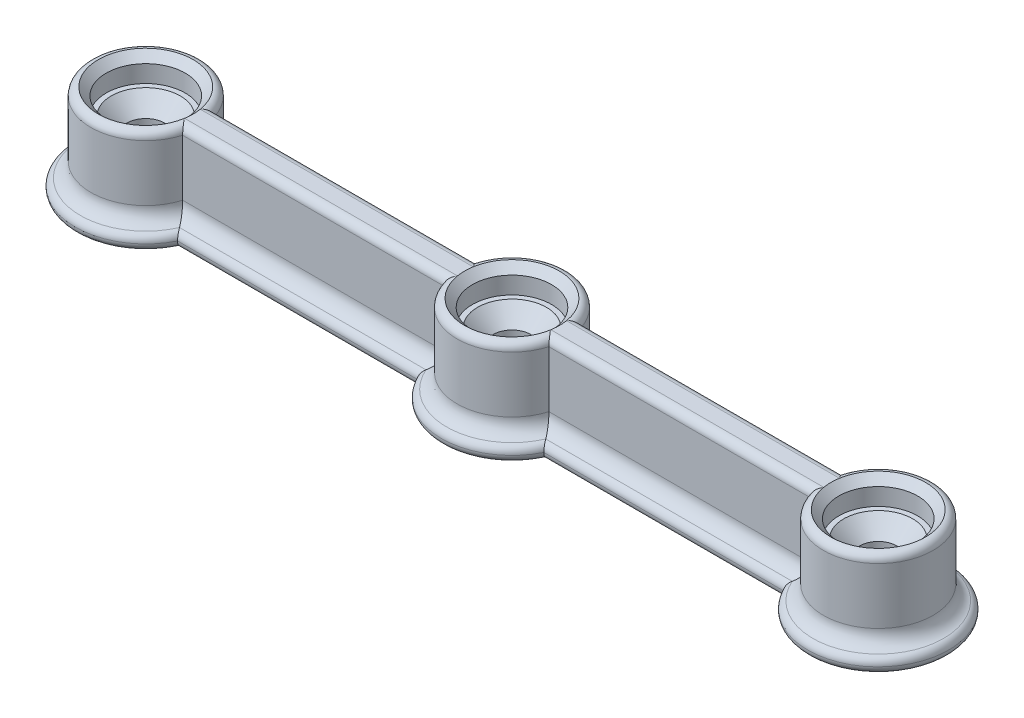
SolidWorks part; units mm, degrees
ref_plane "Front Plane" through (0, 0, 0) normal (0, 0, 1) x (1, 0, 0)
ref_plane "Top Plane" through (0, 0, 0) normal (0, 1, 0) x (1, 0, 0)
ref_plane "Right Plane" through (0, 0, 0) normal (1, 0, 0) x (0, 0, -1)
sketch "Sketch2" plane through (0, 0, 0) normal (0, 1, 0) x (1, 0, 0)
  line L0 (-31.7594, 1.5875) -> (-5.3246, 1.5875)
  line L3 (-31.7594, -1.5875) -> (-5.3246, -1.5875)
  line L4 (5.3246, 1.5875) -> (31.7594, 1.5875)
  line L5 (5.3246, -1.5875) -> (31.7594, -1.5875)
  arc A4 (-5.3246, -1.5875) -> (5.3246, -1.5875) centre (0, 0) ccw
  arc A5 (31.7594, -1.5875) -> (31.7594, 1.5875) centre (37.084, 0) ccw
  arc A6 (-31.7594, 1.5875) -> (-31.7594, -1.5875) centre (-37.084, 0) ccw
  arc A7 (5.3246, 1.5875) -> (-5.3246, 1.5875) centre (0, 0) ccw
  circle A8 centre (-37.084, 0) radius 1.905
  circle A9 centre (0, 0) radius 1.905
  circle A10 centre (37.084, 0) radius 1.905
  circle A11 centre (-37.084, 0) radius 7.366 construction
  circle A12 centre (37.084, 0) radius 7.366 construction
  dimension "D1" = 11.1125
  dimension "D5" = 3.81
  dimension "D4" = 3.175
extrude "Boss-Extrude1" add sketch "Sketch2" along normal blind 9.525
sketch "Sketch4" plane through (0, 0, 0) normal (0, -1, 0) x (1, 0, 0)
  line L9 (-6.3994, 3.175) -> (-30.6846, 3.175)
  line L10 (-30.6846, -3.175) -> (-6.3994, -3.175)
  line L11 (6.3994, -3.175) -> (30.6846, -3.175)
  line L12 (30.6846, 3.175) -> (6.3994, 3.175)
  line L13 (-6.3994, 3.175) -> (-30.6846, 3.175)
  line L14 (-30.6846, -3.175) -> (-6.3994, -3.175)
  line L15 (6.3994, -3.175) -> (30.6846, -3.175)
  line L16 (30.6846, 3.175) -> (6.3994, 3.175)
  line L18 (-5.3246, 1.5875) -> (-31.7594, 1.5875)
  line L19 (-31.7594, -1.5875) -> (-5.3246, -1.5875)
  line L20 (5.3246, -1.5875) -> (31.7594, -1.5875)
  line L21 (31.7594, 1.5875) -> (5.3246, 1.5875)
  line L22 (-5.3246, 1.5875) -> (-31.7594, 1.5875)
  line L23 (-31.7594, -1.5875) -> (-5.3246, -1.5875)
  line L24 (5.3246, -1.5875) -> (31.7594, -1.5875)
  line L25 (31.7594, 1.5875) -> (5.3246, 1.5875)
  arc A8 (6.3994, 3.175) -> (-6.3994, 3.175) centre (0, 0) ccw
  arc A9 (-30.6846, 3.175) -> (-30.6846, -3.175) centre (-37.084, 0) ccw
  arc A10 (-6.3994, -3.175) -> (6.3994, -3.175) centre (0, 0) ccw
  arc A11 (30.6846, -3.175) -> (30.6846, 3.175) centre (37.084, 0) ccw
  arc A12 (6.3994, 3.175) -> (-6.3994, 3.175) centre (0, 0) ccw
  arc A13 (-30.6846, 3.175) -> (-30.6846, -3.175) centre (-37.084, 0) ccw
  arc A14 (-6.3994, -3.175) -> (6.3994, -3.175) centre (0, 0) ccw
  arc A15 (30.6846, -3.175) -> (30.6846, 3.175) centre (37.084, 0) ccw
  arc A16 (5.3246, 1.5875) -> (-5.3246, 1.5875) centre (0, 0) ccw
  arc A17 (-31.7594, 1.5875) -> (-31.7594, -1.5875) centre (-37.084, 0) ccw
  arc A18 (-5.3246, -1.5875) -> (5.3246, -1.5875) centre (0, 0) ccw
  arc A19 (31.7594, -1.5875) -> (31.7594, 1.5875) centre (37.084, 0) ccw
  arc A20 (5.3246, 1.5875) -> (-5.3246, 1.5875) centre (0, 0) ccw
  arc A21 (-31.7594, 1.5875) -> (-31.7594, -1.5875) centre (-37.084, 0) ccw
  arc A22 (-5.3246, -1.5875) -> (5.3246, -1.5875) centre (0, 0) ccw
  arc A23 (31.7594, -1.5875) -> (31.7594, 1.5875) centre (37.084, 0) ccw
  dimension "D1" = 1.5875
  dimension "D2" = 0
extrude "Boss-Extrude2" add sketch "Sketch4" against normal blind 1.5875
sketch "Sketch3" plane through (0, 9.525, 0) normal (0, 1, 0) x (1, 0, 0)
  circle A0 centre (0, 0) radius 4.0005
  circle A1 centre (-37.084, 0) radius 4.0005
  circle A2 centre (37.084, 0) radius 4.0005
  dimension "D1" = 8.001
extrude "Cut-Extrude1" cut sketch "Sketch3" against normal blind 2.54
fillet "Fillet3" radius 0.7937 16 edges at (18.542, 0, 3.175) (44.2277, 0, 0) (18.542, 0, -3.175) (0, 0, -7.1438) (-18.542, 0, -3.175) (-44.2278, 0, 0) (-18.542, 0, 3.175) (0, 0, 7.1437) (-18.542, 1.5875, 3.175) (-44.2278, 1.5875, 0) (-18.542, 1.5875, -3.175) (0, 1.5875, -7.1438) (18.542, 1.5875, -3.175) (44.2277, 1.5875, 0) (18.542, 1.5875, 3.175) (0, 1.5875, 7.1437)
fillet "Fillet1" radius 1.5875 8 edges at (42.6402, 1.5875, 0) (18.542, 1.5875, -1.5875) (0, 1.5875, -5.5563) (-18.542, 1.5875, -1.5875) (-42.6403, 1.5875, 0) (-18.542, 1.5875, 1.5875) (0, 1.5875, 5.5562) (18.542, 1.5875, 1.5875)
fillet "Fillet4" radius 0.7937 8 edges at (-18.542, 9.525, 1.5875) (-42.6403, 9.525, 0) (-18.542, 9.525, -1.5875) (0, 9.525, -5.5562) (18.542, 9.525, -1.5875) (42.6402, 9.525, 0) (18.542, 9.525, 1.5875) (0, 9.525, 5.5562)
chamfer "Chamfer1" distance 1.5875 angle 45 3 edges at (37.084, 6.985, 1.905) (0, 6.985, 1.905) (-37.084, 6.985, 1.905)
chamfer "Chamfer2" distance 0.7937 angle 45 3 edges at (37.084, 9.525, 4.0005) (0, 9.525, 4.0005) (-37.084, 9.525, 4.0005)
